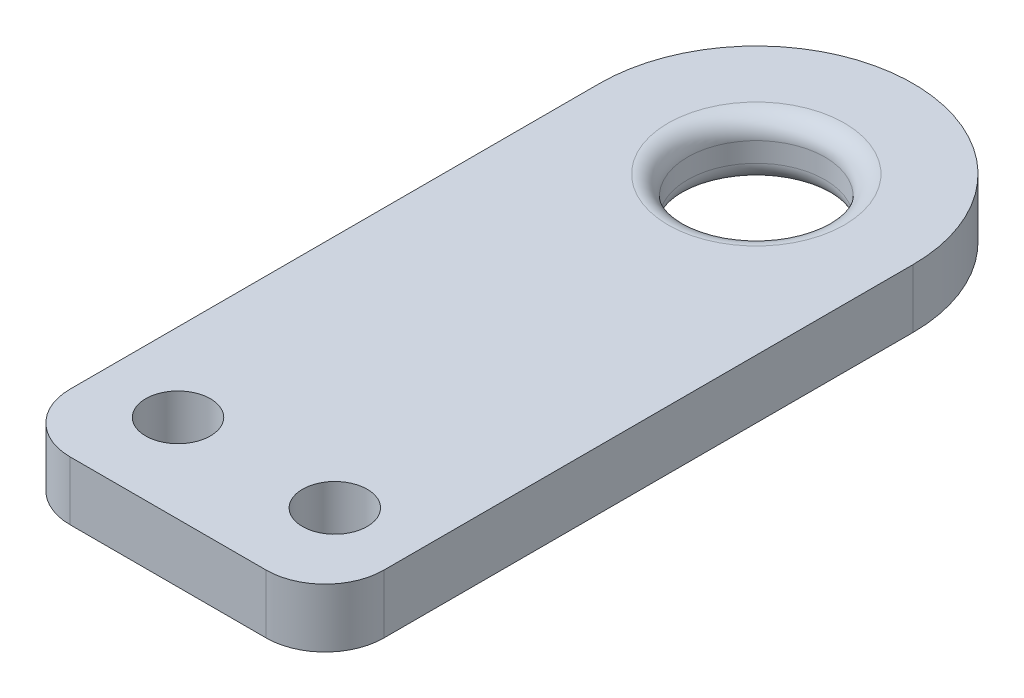
SolidWorks part; units mm, degrees
ref_plane "Plano frontal" through (0, 0, 0) normal (0, 0, 1) x (1, 0, 0)
ref_plane "Plano superior" through (0, 0, 0) normal (0, 1, 0) x (1, 0, 0)
ref_plane "Plano direito" through (0, 0, 0) normal (1, 0, 0) x (0, 0, -1)
sketch "Sketch2" plane through (0, 0, 0) normal (0, 1, 0) x (1, 0, 0)
  circle A0 centre (0, 0) radius 8
  dimension "D1" = 16
extrude "Boss-Extrude1" add sketch "Sketch2" against normal blind 1.5 and the other way blind 1.5
sketch "Sketch3" plane through (0, 0, 0) normal (0, 1, 0) x (1, 0, 0)
  line L1 (-8, 0) -> (8, 0)
  line L2 (-8, 0) -> (-8, -30)
  line L3 (-8, -30) -> (8, -30)
  line L4 (8, 0) -> (8, -30)
  circle A0 centre (0, 0) radius 8 construction
  dimension "D1" = 30
extrude "Boss-Extrude2" add sketch "Sketch3" along normal mid plane 3
sketch "Sketch4" plane through (0, 1.5, 0) normal (0, 1, 0) x (1, 0, 0)
  line L0 (-8, -30) -> (8, -30) construction
  circle A0 centre (4, -25.5) radius 1.65
  circle A1 centre (-4, -25.5) radius 1.65
  dimension "D1" = 3.3
  dimension "D2" = 3.3
  dimension "D3" = 4.5
  dimension "D4" = 4
  dimension "D5" = 4
extrude "Cut-Extrude1" cut sketch "Sketch4" against normal up to next
sketch "Sketch5" plane through (0, -1.5, 0) normal (0, -1, 0) x (1, 0, 0)
  circle A0 centre (0, 0) radius 3.5
  dimension "D1" = 7
extrude "Cut-Extrude2" cut sketch "Sketch5" against normal up to next
fillet "Fillet1" radius 1 2 edges at (0, 1.5, 3.5) (0, -1.5, -3.5)
fillet "Fillet2" radius 3 2 edges at (-8, 0, 30) (8, 0, 30)
equation "\"D2@Sketch4\"=\"D1@Sketch4\""
equation "\"D5@Sketch4\"=\"D4@Sketch4\""
